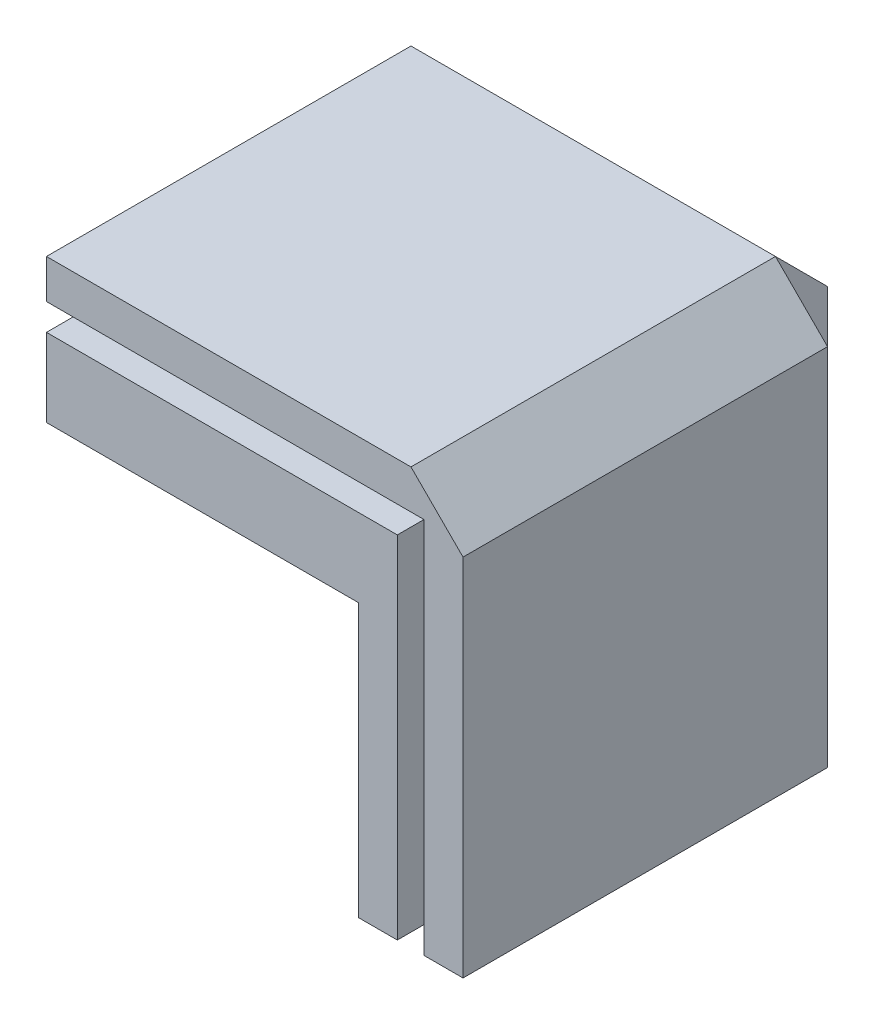
SolidWorks part; units mm, degrees
material "6061-T6 (SS)"
ref_plane "Front Plane" through (0, 0, 0) normal (0, 0, 1) x (1, 0, 0)
ref_plane "Top Plane" through (0, 0, 0) normal (0, 1, 0) x (1, 0, 0)
ref_plane "Right Plane" through (0, 0, 0) normal (1, 0, 0) x (0, 0, -1)
sketch "Sketch4" plane through (0, 0, 0) normal (0, 1, 0) x (1, 0, 0)
  line L1 (0, 0) -> (50.8, 0)
  line L2 (0, 0) -> (0, 50.8)
  line L3 (0, 50.8) -> (50.8, 50.8)
  line L4 (50.8, 0) -> (50.8, 50.8)
  dimension "D1" = 50.8
  dimension "D2" = 50.8
extrude "Boss-Extrude4" add sketch "Sketch4" along normal blind 50.8
sketch "Sketch5" plane through (0, 0, 0) normal (0, -1, 0) x (1, 0, 0)
  line L1 (0, 0) -> (38.0238, 0)
  line L2 (0, 0) -> (0, -38.0238)
  line L3 (0, -38.0238) -> (38.0238, -38.0238)
  line L4 (38.0238, 0) -> (38.0238, -38.0238)
  dimension "D1" = 38.0238
extrude "Cut-Extrude1" cut sketch "Sketch5" against normal blind 38.0238
sketch "Sketch6" plane through (0, 0, 0) normal (-1, 0, 0) x (0, 0, 1)
  line L7 (0, 50.8) -> (0, 38.0238) construction
  line L8 (-50.8, 0) -> (-38.0238, 0) construction
  line L9 (-46.0375, 0) -> (-42.7863, 0)
  line L10 (0, 46.0375) -> (0, 42.7863)
  line L13 (-46.0375, 4.7625) -> (-42.7863, 4.7625)
  line L14 (-42.7863, 4.7625) -> (-42.7863, 42.7863)
  line L15 (-42.7863, 42.7863) -> (-4.7625, 42.7863)
  line L16 (-4.7625, 42.7863) -> (-4.7625, 46.0375)
  line L17 (-4.7625, 46.0375) -> (-46.0375, 46.0375)
  line L18 (-46.0375, 46.0375) -> (-46.0375, 4.7625)
  line L20 (-42.7863, 0) -> (-42.7863, 42.7863)
  line L21 (-42.7863, 42.7863) -> (0, 42.7863)
  line L23 (0, 46.0375) -> (-46.0375, 46.0375)
  line L24 (-46.0375, 46.0375) -> (-46.0375, 0)
  dimension "D1" = 4.7625
extrude "Cut-Extrude2" cut sketch "Sketch6" against normal blind 31.6738
sketch "Sketch7" plane through (0, 0, 0) normal (0, 0, 1) x (1, 0, 0)
  line L0 (31.6738, 46.0375) -> (46.0375, 46.0375)
  line L1 (31.6738, 42.7863) -> (42.7863, 42.7863)
  line L2 (31.6738, 42.7863) -> (31.6738, 46.0375) construction
  line L3 (46.0375, 46.0375) -> (46.0375, 0)
  line L4 (42.7863, 42.7863) -> (42.7863, 0)
  line L5 (38.0238, 0) -> (50.8, 0) construction
  line L6 (42.7863, 0) -> (46.0375, 0)
  line L7 (50.8, 50.8) -> (50.8, 0) construction
  line L8 (38.0238, 38.0238) -> (38.0238, 0) construction
  line L9 (31.6738, 42.7863) -> (0, 42.7863) construction
  point P8 (35.6318, 0.2408)
  dimension "D1" = 4.7625
  dimension "D2" = 4.7625
extrude "Cut-Extrude3" cut sketch "Sketch7" against normal blind 31.6738 and the other way through all
sketch "Sketch8" plane through (0, 0, 0) normal (0, -1, 0) x (1, 0, 0)
  line L0 (31.6738, -46.0375) -> (46.0375, -46.0375)
  line L1 (46.0375, -31.6738) -> (46.0375, -46.0375)
  line L2 (42.7863, -31.6738) -> (42.7863, -42.7863)
  line L3 (31.6738, -42.7863) -> (42.7863, -42.7863)
  line L4 (31.6738, -46.0375) -> (31.6738, -42.7863) construction
  line L5 (31.6738, -42.7863) -> (0, -42.7863) construction
  line L6 (31.6738, -46.0375) -> (31.6738, -42.7863)
  line L7 (42.7863, -31.6738) -> (46.0375, -31.6738)
extrude "Cut-Extrude4" cut sketch "Sketch8" against normal blind 31.6738
chamfer "Chamfer1" distance 6.35 angle 45 3 edges at (50.8, 50.8, -25.4) (50.8, 25.4, -50.8) (25.4, 50.8, -50.8)
sketch "Sketch9" plane through (38.0238, 0, 0) normal (-1, 0, 0) x (0, 0, 1)
  line L0 (0, 38.0238) -> (0, 0) construction
  line L1 (-38.0238, 38.0238) -> (0, 38.0238)
  line L2 (-38.0238, 38.0238) -> (-38.0238, 33.2613)
  line L3 (-38.0238, 33.2613) -> (0, 33.2613)
  line L4 (0, 38.0238) -> (0, 33.2613)
  dimension "D1" = 4.7625
extrude "Boss-Extrude5" add sketch "Sketch9" along normal up to surface (38.0238 mm away) up to face at (0, 26.9367, -26.9367)
sketch "Sketch10" plane through (0, 0, 0) normal (-1, 0, 0) x (0, 0, 1)
  line L1 (-42.7863, 42.7863) -> (-17.0053, 42.7863)
  line L2 (-42.7863, 42.7863) -> (-42.7863, 39.5605)
  line L3 (-42.7863, 39.5605) -> (-17.0053, 39.5605)
  line L4 (-17.0053, 42.7863) -> (-17.0053, 39.5605)
  dimension "D1" = 25.781
  dimension "D2" = 3.2258
extrude "Cut-Extrude5" cut sketch "Sketch10" against normal up to surface (31.6738 mm away) up to face at (31.6738, 40.1659, -40.1659)
